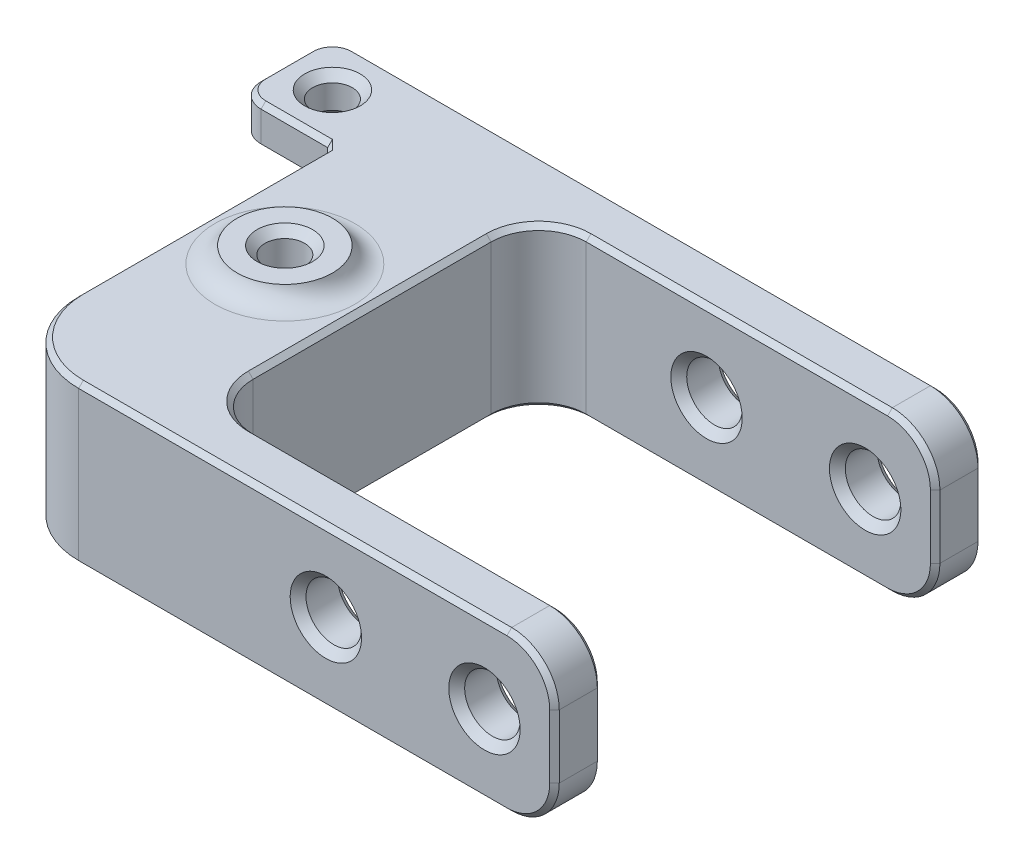
SolidWorks part; units mm, degrees
material "铸造合金钢"
ref_plane "前视基准面" through (0, 0, 0) normal (0, 0, 1) x (1, 0, 0)
ref_plane "上视基准面" through (0, 0, 0) normal (0, 1, 0) x (1, 0, 0)
ref_plane "右视基准面" through (0, 0, 0) normal (1, 0, 0) x (0, 0, -1)
other "Configuration Table"
sketch "草图1" plane through (0, 0, 0) normal (0, 1, 0) x (1, 0, 0)
  line L0 (23.2732, 11.8831) -> (23.2732, 8.8831)
  line L1 (-11.7268, 11.8831) -> (23.2732, 11.8831)
  line L3 (-11.7268, -15.1169) -> (23.2732, -15.1169)
  line L5 (23.2732, 8.8831) -> (-1.7268, 8.8831)
  line L6 (-1.7268, 8.8831) -> (-1.7268, -12.1169)
  line L7 (-1.7268, -12.1169) -> (23.2732, -12.1169)
  line L8 (23.2732, -12.1169) -> (23.2732, -15.1169)
  line L9 (-11.7268, 11.8831) -> (-17.7268, 11.8831)
  line L10 (-17.7268, 11.8831) -> (-17.7268, 5.8831)
  line L11 (-17.7268, 5.8831) -> (-11.7268, 5.8831)
  line L12 (-11.7268, 5.8831) -> (-11.7268, -15.1169)
  dimension "D1" = 27
  dimension "D2" = 3
  dimension "D3" = 3
  dimension "D4" = 6
  dimension "D5" = 6
  dimension "D6" = 10
  dimension "D7" = 25
extrude "凸台-拉伸1" add sketch "草图1" along normal blind 10
sketch "草图2" plane through (0, 0, -11.8831) normal (0, 0, -1) x (-1, 0, 0)
  line L0 (-23.2732, 5) -> (17.7268, 5) construction
  line L1 (-23.2732, 10) -> (-23.2732, 0) construction
  line L2 (17.7268, 10) -> (17.7268, 0) construction
  circle A0 centre (-18.8586, 5) radius 1.75
  circle A1 centre (-8.8586, 5) radius 1.75
  dimension "D1" = 3.5
  dimension "D2" = 10
extrude "切除-拉伸1" cut sketch "草图2" against normal blind 28
sketch "草图3" plane through (0, 0, -5.8831) normal (0, 0, 1) x (1, 0, 0)
  line L0 (-17.7268, 7.5) -> (-11.7268, 7.5)
  line L1 (-17.7268, 10) -> (-17.7268, 0) construction
  line L2 (-11.7268, 10) -> (-11.7268, 0) construction
  line L3 (-11.7268, 7.5) -> (-11.7268, 2.3478)
  line L4 (-11.7268, 2.3478) -> (-17.7268, 2.3478)
  line L5 (-17.7268, 2.3478) -> (-17.7268, 7.5)
  line L6 (-17.7268, 4.9239) -> (-11.7268, 4.9239) construction
  line L7 (-17.7268, 10) -> (-11.7268, 10) construction
  dimension "D1" = 2.5
extrude "切除-拉伸2" cut sketch "草图3" against normal blind 8
sketch "草图4" plane through (0, 10, 0) normal (0, 1, 0) x (1, 0, 0)
  line L0 (-14.7268, 5.8831) -> (-14.7268, 11.8831) construction
  line L1 (-17.7268, 5.8831) -> (-11.7268, 5.8831) construction
  line L2 (23.2732, 11.8831) -> (-17.7268, 11.8831) construction
  circle A0 centre (-14.7268, 8.8831) radius 1.25
  dimension "D1" = 2.5
extrude "切除-拉伸3" cut sketch "草图4" against normal blind 11 contours A0
fillet "圆角1" radius 3 4 edges at (23.2732, 0, 13.6169) (23.2732, 10, 13.6169) (23.2732, 0, -10.3831) (23.2732, 10, -10.3831)
fillet "圆角2" radius 5 1 edges at (-11.7268, 5, 15.1169)
fillet "圆角3" radius 1.5 4 edges at (-17.7268, 8.75, -5.8831) (-17.7268, 1.1739, -5.8831) (-17.7268, 8.75, -11.8831) (-17.7268, 1.1739, -11.8831)
sketch "草图5" plane through (0, 0, 0) normal (0, -1, 0) x (1, 0, 0)
  line L0 (-11.7268, 2.1169) -> (-1.7268, 2.1169) construction
  line L1 (-11.7268, -5.8831) -> (-11.7268, 10.1169) construction
  line L2 (-1.7268, 12.1169) -> (-1.7268, -8.8831) construction
  circle A0 centre (-6.7268, 2.1169) radius 3
  dimension "D1" = 6
extrude "凸台-拉伸2" add sketch "草图5" along normal blind 1 contours A0
sketch "草图6" plane through (0, 10, 0) normal (0, 1, 0) x (1, 0, 0)
  circle A0 centre (-6.7268, -2.1169) radius 3
  circle A1 centre (-6.7268, -2.1169) radius 3 construction
extrude "凸台-拉伸3" add sketch "草图6" along normal blind 1 contours A0
fillet "圆角4" radius 1.5 2 edges at (-6.7268, 0, 5.1169) (-6.7268, 10, 5.1169)
sketch "草图7" plane through (0, -1, 0) normal (0, -1, 0) x (1, 0, 0)
  circle A0 centre (-6.7268, 2.1169) radius 1.25
  dimension "D1" = 2.5
extrude "切除-拉伸4" cut sketch "草图7" against normal blind 17
chamfer "倒角1" distance 0.5 angle 45 14 edges at (-14.7268, 0, -7.6331) (-14.7268, 2.3478, -10.1331) (-14.7268, 7.5, -7.6331) (-14.7268, 10, -7.6331) (-6.7268, -1, 0.8669) (-6.7268, 11, 3.3669) (7.1086, 5, -8.8831) (7.1086, 5, -11.8831) (17.1086, 5, -8.8831) (17.1086, 5, -11.8831) (7.1086, 5, 15.1169) (10.6086, 5, 12.1169) (17.1086, 5, 15.1169) (20.6086, 5, 12.1169)
fillet "圆角5" radius 3 2 edges at (-1.7268, 5, -8.8831) (-1.7268, 5, 12.1169)
chamfer "倒角2" distance 0.3 angle 45 53 edges at (-13.9768, 7.5, -11.8831) (-17.2874, 7.5, -11.4438) (-17.7268, 7.5, -8.8831) (-11.7268, 7.5, -8.8831) (-17.2874, 7.5, -6.3225) (-11.7268, 8.75, -5.8831) (-13.9768, 7.5, -5.8831) (-13.9768, 2.3478, -11.8831) (-17.2874, 2.3478, -11.4438) (-17.7268, 2.3478, -8.8831) (-11.7268, 2.3478, -8.8831) (-17.2874, 2.3478, -6.3225) (-11.7268, 1.1739, -5.8831) (-13.9768, 2.3478, -5.8831) (-11.7268, 4.9239, -11.8831) (-11.7268, 10, 2.1169) (-10.2623, 10, 13.6524) (6.7732, 10, 15.1169) (22.3945, 9.1213, 15.1169) (-11.7268, 0, 2.1169) (23.2732, 5, 15.1169) (-10.2623, 0, 13.6524) (22.3945, 0.8787, 15.1169) (6.7732, 0, 15.1169) (-13.9768, 10, -5.8831) (-17.2874, 10, -6.3225) (-17.7268, 10, -8.8831) (-17.2874, 10, -11.4438) (2.0232, 10, -11.8831) (-13.9768, 0, -5.8831) (22.3945, 9.1213, -11.8831) (-17.2874, 0, -6.3225) (23.2732, 5, -11.8831) (-17.7268, 0, -8.8831) (22.3945, 0.8787, -11.8831) (-17.2874, 0, -11.4438) (2.0232, 0, -11.8831) (10.7732, 0, 12.1169) (22.3945, 0.8787, 12.1169) (-0.8481, 0, 11.2382) (23.2732, 5, 12.1169) (-1.7268, 0, 1.6169) (22.3945, 9.1213, 12.1169) (-0.8481, 0, -8.0045) (10.7732, 10, 12.1169) (10.7732, 0, -8.8831) (-0.8481, 10, 11.2382) (22.3945, 0.8787, -8.8831) (-1.7268, 10, 1.6169) (23.2732, 5, -8.8831) (-0.8481, 10, -8.0045) (22.3945, 9.1213, -8.8831) (10.7732, 10, -8.8831)
